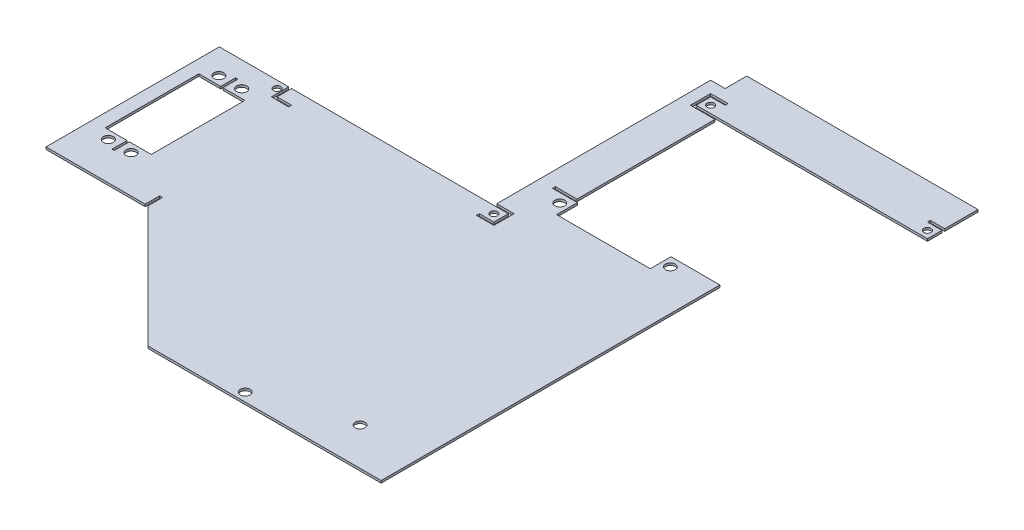
SolidWorks part; units mm, degrees
ref_plane "Front Plane" through (0, 0, 0) normal (0, 0, 1) x (1, 0, 0)
ref_plane "Top Plane" through (0, 0, 0) normal (0, 1, 0) x (1, 0, 0)
ref_plane "Right Plane" through (0, 0, 0) normal (1, 0, 0) x (0, 0, -1)
sketch "Sketch2" plane through (0, 0, 0) normal (0, 1, 0) x (1, 0, 0)
  line L1 (-127, -127) -> (127, -127)
  line L2 (-127, -127) -> (-127, 127)
  line L3 (-127, 127) -> (127, 127)
  line L4 (127, -127) -> (127, 127)
  line L5 (-127, -127) -> (127, 127) construction
  line L6 (-127, 127) -> (127, -127) construction
  point P0 (0, 0)
  dimension "D1" = 254
  dimension "D2" = 254
extrude "Boss-Extrude1" add sketch "Sketch2" along normal blind 1.0008 contours L3 L4 L1 L2
sketch "Sketch3" plane through (0, 1.0008, 0) normal (0, 1, 0) x (1, 0, 0)
  line L0 (57.15, 41.91) -> (57.15, 3.81) construction
  line L1 (127, 47.252) -> (50.8, 47.252)
  line L2 (127, 47.252) -> (127, 21.852)
  line L3 (127, 21.852) -> (50.8, 21.852)
  line L4 (50.8, 47.252) -> (50.8, 21.852)
  line L7 (57.746, 22.36) -> (64.35, 22.36) construction
  line L8 (57.746, 22.36) -> (64.35, 22.36) construction
  dimension "D1" = 6.35
  dimension "D2" = 0.508
  dimension "D3" = 25.4
extrude "Cut-Extrude1" cut sketch "Sketch3" against normal through all both and the other way through all
sketch "Sketch4" plane through (0, 1.0008, 0) normal (0, 1, 0) x (1, 0, 0)
  line L6 (127, -127) -> (127, 21.852)
  line L8 (127, 21.852) -> (50.8, 21.852)
  line L9 (127, 127) -> (-127, 127)
  line L10 (-127, 127) -> (-127, -127)
  line L11 (-127, -127) -> (127, -127)
  line L12 (127, -127) -> (127, 21.852)
  line L17 (119.3189, -127) -> (127, -127)
  line L18 (127, 21.852) -> (128.99, 21.852)
  line L19 (50.8, 21.852) -> (50.8, 47.252)
  line L22 (50.8, 47.252) -> (127, 47.252)
  line L24 (127, 47.252) -> (127, 127)
  arc A0 (120.65, 9.832) -> (120.65, -129.212) centre (233.68, -59.69) ccw construction
  arc A1 (128.99, 21.852) -> (119.3189, -127) centre (233.68, -59.69) ccw
  dimension "D1" = 0
extrude "Cut-Extrude2" cut sketch "Sketch4" against normal through all both rebuild error yes
sketch "Sketch5" plane through (0, 1.0008, 0) normal (0, 1, 0) x (1, 0, 0)
  line L0 (57.15, -129.54) -> (57.15, -61.2891) construction
  circle A0 centre (109.227, 17.86) radius 2.1 construction
  circle A1 centre (60.627, 17.86) radius 2.1 construction
  circle A2 centre (109.227, 17.86) radius 2.1 construction
  circle A3 centre (60.627, 17.86) radius 2.1 construction
  circle A4 centre (63.5, -123.19) radius 2.15
  circle A5 centre (101.2179, -110.49) radius 2.15
  circle A6 centre (60.627, 17.86) radius 2.15
  circle A7 centre (109.227, 17.86) radius 2.15
  dimension "D1" = 6.35
  dimension "D5" = 4.3
  dimension "D2" = 12.7
  dimension "D3" = 6.35
  dimension "D4" = 6.35
extrude "Cut-Extrude3" cut sketch "Sketch5" against normal through all both
sketch "Sketch6" plane through (0, 1.0008, 0) normal (0, 1, 0) x (1, 0, 0)
  line L12 (64.35, 22.36) -> (64.35, 12.733)
  line L13 (64.35, 12.733) -> (105.504, 12.733)
  line L14 (105.504, 12.733) -> (105.504, 22.36)
  line L15 (105.504, 22.36) -> (112.108, 22.36)
  line L16 (112.108, 22.36) -> (112.108, 23.36)
  line L17 (112.108, 23.36) -> (105.504, 23.36)
  line L18 (105.504, 23.36) -> (105.504, 32.987)
  line L19 (105.504, 32.987) -> (64.35, 32.987)
  line L20 (64.35, 32.987) -> (64.35, 23.36)
  line L21 (64.35, 23.36) -> (57.746, 23.36)
  line L22 (57.746, 23.36) -> (57.746, 22.36)
  line L23 (57.746, 22.36) -> (64.35, 22.36)
  line L24 (64.35, 22.36) -> (64.35, 12.733)
  line L25 (64.35, 12.733) -> (105.504, 12.733)
  line L26 (105.504, 12.733) -> (105.504, 22.36)
  line L27 (105.504, 22.36) -> (112.108, 22.36)
  line L28 (112.108, 22.36) -> (112.108, 23.36)
  line L29 (112.108, 23.36) -> (105.504, 23.36)
  line L30 (105.504, 23.36) -> (105.504, 32.987)
  line L31 (105.504, 32.987) -> (64.35, 32.987)
  line L32 (64.35, 32.987) -> (64.35, 23.36)
  line L33 (64.35, 23.36) -> (57.746, 23.36)
  line L34 (57.746, 23.36) -> (57.746, 22.36)
  line L35 (57.746, 22.36) -> (64.35, 22.36)
  circle A1 centre (60.627, 27.86) radius 2.1
  circle A2 centre (60.627, 27.86) radius 2.1
  circle A3 centre (60.627, 17.86) radius 2.1
  circle A4 centre (60.627, 17.86) radius 2.1
  circle A5 centre (109.227, 27.86) radius 2.1
  circle A6 centre (109.227, 27.86) radius 2.1
  circle A7 centre (109.227, 17.86) radius 2.1
  circle A8 centre (109.227, 17.86) radius 2.1
  dimension "D1" = 0
  dimension "D2" = 0
  dimension "D3" = 0
  dimension "D4" = 0
  dimension "D5" = 0
extrude "Cut-Extrude4" cut sketch "Sketch6" against normal through all both
sketch "Sketch7" plane through (0, 1.0008, 0) normal (0, 1, 0) x (1, 0, 0)
  line L1 (-41.8592, 2.4892) -> (53.3908, 2.4892)
  line L2 (-41.8592, 2.4892) -> (-41.8592, 97.7392)
  line L3 (-41.8592, 97.7392) -> (53.3908, 97.7392)
  line L4 (53.3908, 2.4892) -> (53.3908, 97.7392)
  line L5 (-41.8592, 2.4892) -> (53.3908, 97.7392) construction
  line L6 (-41.8592, 97.7392) -> (53.3908, 2.4892) construction
  circle A2 centre (95.25, 22.86) radius 4.7625 construction
  circle A3 centre (95.25, 22.86) radius 4.699 construction
  point P0 (5.7658, 50.1142)
  dimension "D1" = 95.25
  dimension "D3" = 20.3708
  dimension "D2" = 137.1092
extrude "Cut-Extrude5" cut sketch "Sketch7" against normal through all both
sketch "Sketch8" plane through (0, 1.0008, 0) normal (0, 1, 0) x (1, 0, 0)
  line L0 (127, 47.252) -> (127, 127)
  line L2 (127, 127) -> (-127, 127)
  line L3 (-127, 127) -> (-127, -127)
  line L4 (-127, -127) -> (-41.8592, -127)
  line L5 (-127, -127) -> (127, -127) construction
  line L6 (-41.8592, -127) -> (-41.8592, 47.252)
  line L7 (-41.8592, 47.252) -> (127, 47.252)
  line L9 (-41.8592, 97.7392) -> (-41.8592, 2.4892) construction
extrude "Cut-Extrude6" cut sketch "Sketch8" against normal through all both
sketch "Sketch17" plane through (0, 1.0008, 0) normal (0, 1, 0) x (1, 0, 0)
  line L1 (53.3908, 2.4892) -> (47.0408, 2.4892)
  line L2 (53.3908, 2.4892) -> (53.3908, 85.0392)
  line L3 (59.7408, 97.7392) -> (47.0408, 97.7392)
  line L4 (47.0408, 2.4892) -> (47.0408, 97.7392)
  line L5 (-41.8592, 2.4892) -> (53.3908, 2.4892) construction
  line L6 (59.7408, 97.7392) -> (154.9908, 97.7392)
  line L8 (53.3908, 85.0392) -> (154.9908, 85.0392)
  line L9 (154.9908, 97.7392) -> (154.9908, 85.0392)
  dimension "D1" = 12.7
extrude "Boss-Extrude4" add sketch "Sketch17" against normal up to surface (1.0008 mm away) up to face at (61.6771, 0, 13.6148)
sketch "Sketch18" plane through (0, 1.0008, 0) normal (0, 1, 0) x (1, 0, 0)
  line L0 (47.0408, 2.4892) -> (53.3908, 2.4892)
extrude "Cut-Extrude-Thin4" cut sketch "Sketch18" against normal through all both and the other way through all thin thin type one direction reverse wall 1.27
sketch "Sketch9" plane through (0, 1.0008, 0) normal (0, 1, 0) x (1, 0, 0)
  line L0 (-41.8592, -60.5651) -> (24.5757, -127)
  line L1 (-41.8592, -127) -> (-41.8592, 2.4892) construction
  line L2 (-41.8592, -127) -> (127, -127) construction
  line L3 (-41.8592, -127) -> (24.5757, -127)
  line L4 (-41.8592, -127) -> (-41.8592, -60.5651)
  circle A0 centre (95.377, 22.86) radius 149.6811 construction
  circle A1 centre (95.377, 22.86) radius 156.0311 construction
  dimension "D1" = 6.35
  dimension "D2" = 45
extrude "Cut-Extrude7" cut sketch "Sketch9" against normal through all both
sketch "Sketch10" plane through (0, 1.0008, 0) normal (0, 1, 0) x (1, 0, 0)
  line L37 (53.3908, 21.852) -> (53.3908, 85.0392) construction
  line L38 (53.3908, 83.7692) -> (62.9158, 83.7692)
  line L39 (53.3908, 83.7692) -> (53.3908, 23.122)
  line L40 (53.3908, 23.122) -> (62.9158, 23.122)
  line L41 (62.9158, 83.7692) -> (62.9158, 23.122)
  line L42 (64.35, 21.852) -> (53.3908, 21.852) construction
  line L43 (53.3908, 85.0392) -> (154.9908, 85.0392) construction
  line L44 (154.9908, 97.7392) -> (47.0408, 97.7392) construction
  line L45 (53.3908, 97.7392) -> (154.9908, 97.7392)
  line L46 (53.3908, 97.7392) -> (53.3908, 107.2642)
  line L47 (53.3908, 107.2642) -> (154.9908, 107.2642)
  line L48 (154.9908, 97.7392) -> (154.9908, 107.2642)
  line M23 (-41.8592, -60.5651) -> (24.5757, -127)
  line M24 (24.5757, -127) -> (127, -127)
  line M33 (-41.8592, 2.4892) -> (-41.8592, -60.5651)
  dimension "D1" = 1.27
  dimension "D2" = 1.27
  dimension "D3" = 9.525
extrude "Boss-Extrude2" add sketch "Sketch10" against normal up to surface (1.0008 mm away) contours M23 | M24 | M33 | L46 L45 L48 L47 | L39 L38 L41 L40 up to face at (67.776, 0, -10.3743)
sketch "Sketch14" plane through (0, 1.0008, 0) normal (0, 1, 0) x (1, 0, 0)
  line L0 (-67.8612, -12.271) -> (-47.6072, -53.425) construction
  line L5 (-67.8612, -12.271) -> (-58.2342, -12.271)
  line L6 (-67.8612, -12.271) -> (-67.8612, -53.425)
  line L7 (-67.8612, -53.425) -> (-58.2342, -53.425)
  line L12 (-47.6072, -12.271) -> (-47.6072, -53.425)
  line L17 (-41.8592, -5.1308) -> (-73.6092, -5.1308)
  line L22 (-41.8592, -60.5651) -> (-41.8592, 2.4892) construction
  line L23 (-73.6092, -5.1308) -> (-73.6092, -60.5651)
  line L24 (-73.6092, -60.5651) -> (-41.8592, -60.5651)
  line L25 (-41.8592, -60.5651) -> (-41.8592, -5.1308)
  line L34 (-47.6072, -12.271) -> (-67.8612, -53.425) construction
  line L35 (-62.7342, -8.548) -> (-52.7342, -57.148) construction
  line L36 (-62.7342, -57.148) -> (-52.7342, -8.548) construction
  line L37 (-57.2342, -53.425) -> (-47.6072, -53.425)
  line L38 (-58.2342, -53.425) -> (-58.2342, -60.029)
  line L39 (-58.2342, -60.029) -> (-57.2342, -60.029)
  line L40 (-57.2342, -53.425) -> (-57.2342, -60.029)
  line L41 (-57.7342, -32.848) -> (-15.6253, -32.848) construction
  line L42 (-58.2342, -5.667) -> (-57.2342, -5.667)
  line L43 (-58.2342, -12.271) -> (-58.2342, -5.667)
  line L44 (-57.2342, -12.271) -> (-57.2342, -5.667)
  line L45 (-57.2342, -12.271) -> (-47.6072, -12.271)
  line L47 (-73.6092, -5.1308) -> (-73.6092, 2.4892)
  line L48 (-73.6092, 2.4892) -> (-41.8592, 2.4892)
  line L49 (-41.8592, 2.4892) -> (-41.8592, -5.1308)
  line L51 (-41.8592, 2.4892) -> (53.3908, 2.4892) construction
  line L52 (-73.6092, -60.5651) -> (-73.6092, -73.66)
  line L53 (-73.6092, -73.66) -> (-28.7643, -73.66)
  line L54 (24.5757, -127) -> (-41.8592, -60.5651) construction
  line L57 (-28.7643, -73.66) -> (-41.8592, -60.5651)
  circle A8 centre (-62.7342, -57.148) radius 2.2
  circle A9 centre (-52.7342, -57.148) radius 2.2
  circle A10 centre (-62.7342, -8.548) radius 2.2
  circle A11 centre (-52.7342, -8.548) radius 2.2
  point P9 (-57.7342, -60.029)
  point P19 (-57.7342, -32.848)
  point P20 (-57.7342, -32.848)
  point P37 (-73.6092, -32.848)
  point P39 (-57.7342, -60.5651)
  dimension "D3" = 48.6
  dimension "D4" = 4.4
  dimension "D2" = 10
  dimension "D5" = 41.154
  dimension "D6" = 20.254
  dimension "D7" = 1
  dimension "D8" = 6.604
  dimension "D9" = 31.75
  dimension "D10" = 7.62
  dimension "D11" = 53.34
extrude "Boss-Extrude3" add sketch "Sketch14" against normal up to surface (1.0008 mm away) contours L49 L48 L47 L17 | L24 L25 L17 L23 A11 A10 A9 A8 L44 L45 L12 L37 L40 L39 L38 L7 L6 L5 L43 L42 | L24 region at (-42.498, 1.0008, 32.848) region at (-57.7342, 1.0008, 1.3208) region at (-54.2739, 1.0008, 67.4857) up to face at (64.8516, 0, -26.2901)
sketch "Sketch15" plane through (0, 1.0008, 0) normal (0, 1, 0) x (1, 0, 0)
  line L0 (-28.7643, -73.66) -> (-28.7643, -67.31)
  dimension "D1" = 6.35
extrude "Cut-Extrude-Thin3" cut sketch "Sketch15" against normal through all both and the other way through all thin thin type one direction reverse wall 1.27
sketch "Sketch19" plane through (0, 1.0008, 0) normal (0, 1, 0) x (1, 0, 0)
  line L0 (154.9908, 85.0392) -> (154.9908, 107.2642) construction
  line L1 (53.3908, 85.0392) -> (154.9908, 85.0392) construction
  line L2 (53.3908, 83.7692) -> (53.3908, 85.0392) construction
  line L3 (-73.6092, 2.4892) -> (53.3908, 2.4892) construction
  line L4 (53.3908, 2.4892) -> (53.3908, 3.7592) construction
  line L5 (56.5658, 88.2142) -> (151.8158, 88.2142) construction
  line L6 (-45.0342, -0.6858) -> (50.2158, -0.6858) construction
  circle A0 centre (50.2158, -0.6858) radius 1.5875
  circle A1 centre (-45.0342, -0.6858) radius 1.5875
  circle A2 centre (151.8158, 88.2142) radius 1.5875
  circle A3 centre (56.5658, 88.2142) radius 1.5875
  dimension "D3" = 3.175
  dimension "D1" = 3.175
  dimension "D2" = 3.175
  dimension "D4" = 3.175
  dimension "D5" = 3.175
  dimension "D6" = 3.175
extrude "Cut-Extrude8" cut sketch "Sketch19" against normal through all both and the other way through all
sketch "Sketch20" plane through (0, 1.0008, 0) normal (0, 1, 0) x (1, 0, 0)
  line L0 (-41.8592, 2.4892) -> (-41.8592, -3.8608)
  line L1 (-73.6092, 2.4892) -> (53.3908, 2.4892) construction
  line L2 (-41.8592, -3.8608) -> (-35.5092, -3.8608)
  line L3 (53.3908, 2.4892) -> (53.3908, -3.8608)
  line L4 (53.3908, -3.8608) -> (47.0408, -3.8608)
  line L5 (53.3908, 85.0392) -> (53.3908, 91.3892)
  line L6 (53.3908, 91.3892) -> (59.7408, 91.3892)
  line L7 (154.9908, 91.3892) -> (154.9908, 85.0392) construction
  line L8 (148.6408, 91.3892) -> (154.9908, 91.3892)
  line L9 (154.9908, 85.0392) -> (154.9908, 107.2642) construction
  line L10 (52.1208, 85.0392) -> (52.1208, 92.6592)
  line L11 (52.1208, 92.6592) -> (59.7408, 92.6592)
  line L12 (148.6408, 92.6592) -> (154.9908, 92.6592)
  line L13 (54.6608, 2.4892) -> (54.6608, -5.1308)
  line L14 (54.6608, -5.1308) -> (47.0408, -5.1308)
  line L15 (-43.1292, 2.4892) -> (-43.1292, -5.1308)
  line L16 (-43.1292, -5.1308) -> (-35.5092, -5.1308)
  line L17 (-43.1292, 2.4892) -> (-41.8592, 2.4892)
  line L18 (-35.5092, -3.8608) -> (-35.5092, -5.1308)
  line L19 (148.6408, 92.6592) -> (148.6408, 91.3892)
  line L20 (154.9908, 91.3892) -> (154.9908, 92.6592)
  line L21 (53.3908, 85.0392) -> (52.1208, 85.0392)
  line L22 (59.7408, 91.3892) -> (59.7408, 92.6592)
  line L23 (53.3908, 2.4892) -> (54.6608, 2.4892)
  line L24 (47.0408, -3.8608) -> (47.0408, -5.1308)
  line L25 (53.3908, 85.0392) -> (53.3908, 83.7692)
  line L26 (53.3908, 83.7692) -> (62.9158, 83.7692) construction
  line L27 (53.3908, 83.7692) -> (52.1208, 83.7692)
  line L28 (52.1208, 83.7692) -> (52.1208, 85.0392)
  line L29 (53.3908, 2.4892) -> (53.3908, 3.7592)
  line L30 (53.3908, 3.7592) -> (54.6608, 3.7592)
  line L31 (54.6608, 3.7592) -> (54.6608, 2.4892)
  dimension "D1" = 6.35
  dimension "D2" = 95.25
  dimension "D3" = 1.27
  dimension "D4" = 1.27
extrude "Cut-Extrude12" cut sketch "Sketch20" against normal through all both contours L28 L27 L25 L21 | L6 L22 L11 L10 L21 L5 | L31 L30 L29 L23 | L4 L24 L14 L13 L23 L3 | L18 L2 L0 L17 L15 L16 | L8 L20 L12 L19 region at (-41.967, 1.0008, 0.6858) region at (54.0258, 1.0008, -2.3814) region at (54.0258, 1.0008, -3.1242) region at (52.7558, 1.0008, -85.147) region at (52.7558, 1.0008, -84.4042)
equation "\"looseTol\"= 0.02in"
equation "\"tightTol\"= 0.005in"
equation "\"normTol\"= 0.01in"
equation "\"D2@Sketch3\"=\"looseTol\""
equation "\"D5@Sketch5\"=4.3mm"
